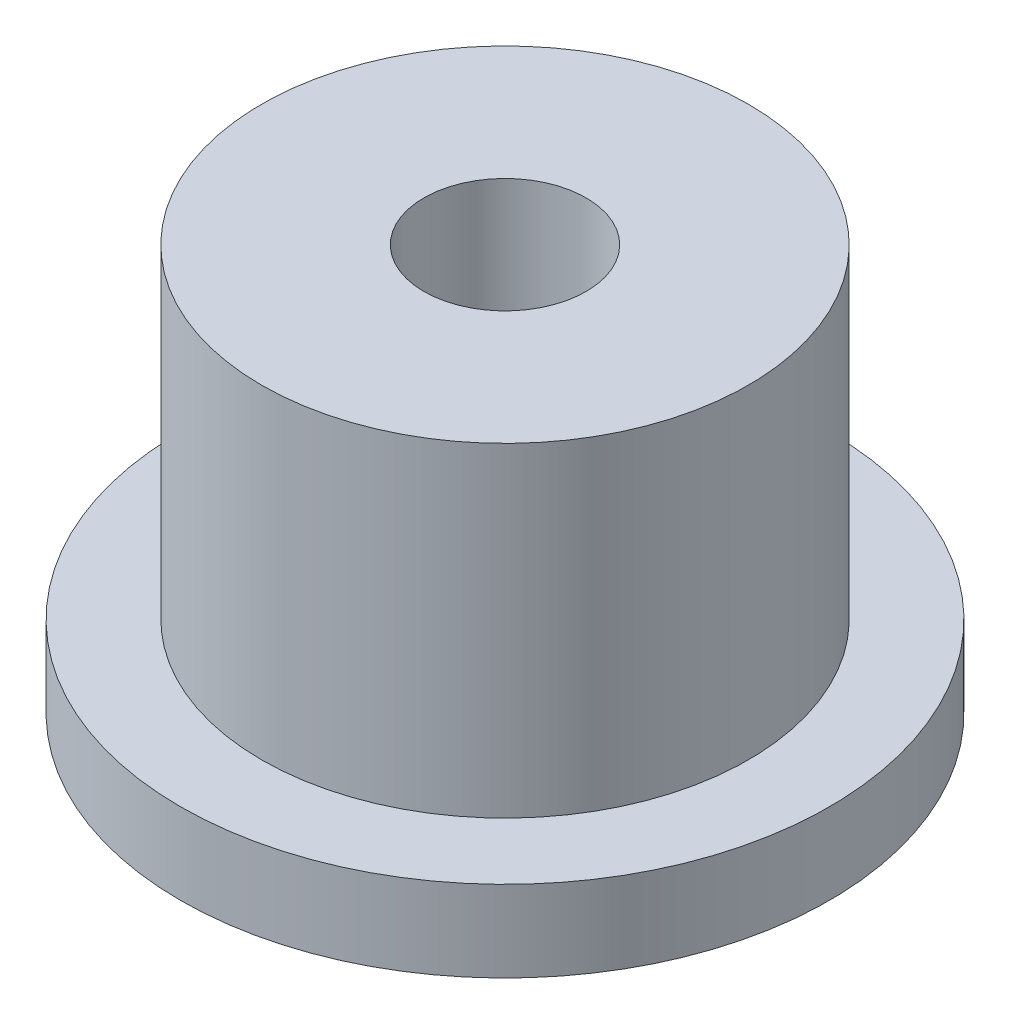
SolidWorks part; units mm, degrees
ref_plane "Front Plane" through (0, 0, 0) normal (0, 0, 1) x (1, 0, 0)
ref_plane "Top Plane" through (0, 0, 0) normal (0, 1, 0) x (1, 0, 0)
ref_plane "Right Plane" through (0, 0, 0) normal (1, 0, 0) x (0, 0, -1)
sketch "Sketch1" plane through (0, 0, 0) normal (0, 1, 0) x (1, 0, 0)
  circle A0 centre (0, 0) radius 100
  circle A1 centre (0, 0) radius 75
  circle A2 centre (0, 0) radius 25
  dimension "D1" = 200
  dimension "D2" = 150
  dimension "D3" = 50
extrude "Boss-Extrude1" add sketch "Sketch1" along normal blind 25 contours A0 A1 region at (-97.1716, 0, 0)
extrude "Boss-Extrude2" add sketch "Sketch1<3>" along normal blind 125 contours A1 A2 region at (-72.8787, 0, 0)
sketch "Sketch1<3>" plane through (0, 0, 0) normal (0, 1, 0) x (1, 0, 0) same geometry as "Sketch1"
